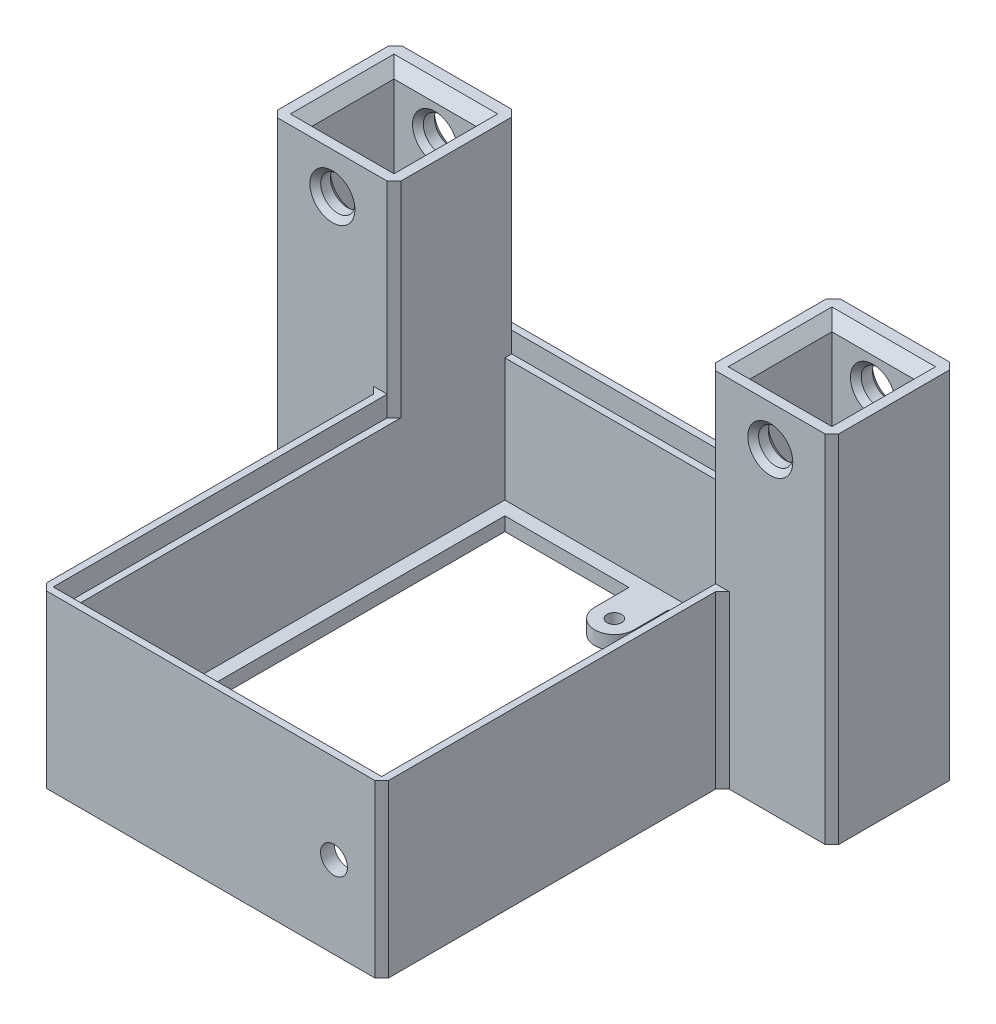
SolidWorks part; units mm, degrees
ref_plane "Front Plane" through (0, 0, 0) normal (0, 0, 1) x (1, 0, 0)
ref_plane "Top Plane" through (0, 0, 0) normal (0, 1, 0) x (1, 0, 0)
ref_plane "Right Plane" through (0, 0, 0) normal (1, 0, 0) x (0, 0, -1)
sketch "Sketch3" plane through (0, 0, 0) normal (0, 1, 0) x (-1, 0, 0)
  line L1 (0, 0) -> (63.5, 0)
  line L2 (0, 0) -> (0, 86.36)
  line L3 (0, 86.36) -> (63.5, 86.36)
  line L4 (63.5, 0) -> (63.5, 86.36)
  dimension "D1" = 86.36
  dimension "D2" = 63.5
extrude "Boss-Extrude2" add sketch "Sketch3" against normal blind 31.75
sketch "Sketch4" plane through (0, -31.75, 0) normal (0, -1, 0) x (1, 0, 0)
  line L1 (-2.54, 83.82) -> (-60.96, 83.82)
  line L2 (-2.54, 83.82) -> (-2.54, 2.54)
  line L3 (-2.54, 2.54) -> (-60.96, 2.54)
  line L4 (-60.96, 83.82) -> (-60.96, 2.54)
  line L8 (-63.5, 86.36) -> (0, 86.36) construction
  line L9 (0, 0) -> (-63.5, 0) construction
  line L10 (0, 86.36) -> (0, 0) construction
  line L11 (-63.5, 0) -> (-63.5, 86.36) construction
  dimension "D1" = 2.54
  dimension "D2" = 2.54
  dimension "D3" = 2.54
  dimension "D4" = 2.54
extrude "Cut-Extrude2" cut sketch "Sketch4" against normal offset from surface (27.94 mm away) 3.81 up to face at (-31.75, 0, 43.18)
sketch "Sketch5" plane through (-63.5, 0, 0) normal (1, 0, 0) x (0, 0, -1)
  line L0 (-86.36, -31.75) -> (-86.36, 0) construction
  line L5 (0, -31.75) -> (-86.36, -31.75) construction
  circle A0 centre (-76.327, -19.177) radius 5.715
  dimension "D1" = 11.43
  dimension "D2" = 6.858
  dimension "D3" = 4.318
extrude "Power Jack Hole" cut sketch "Sketch5" along normal up to next
sketch "Sketch6" plane through (-63.5, 0, 0) normal (-1, 0, 0) x (0, 0, 1)
  line L0 (46.54, 0) -> (46.54, 36.83)
  line L1 (46.54, 36.83) -> (0, 36.83)
  line L2 (0, 36.83) -> (0, 34.29)
  line L3 (0, 34.29) -> (44, 34.29)
  line L4 (44, 34.29) -> (44, 0)
  line L5 (0, 0) -> (86.36, 0) construction
  line L6 (44, 0) -> (46.54, 0)
  line L7 (0, -31.75) -> (0, 0) construction
  dimension "D1" = 44
  dimension "D2" = 34.29
  dimension "D3" = 2.54
  dimension "D4" = 2.54
extrude "Motor Mounting Shape" add sketch "Sketch6" against normal up to surface (63.5 mm away) up to face at (0, -15.875, 43.18)
sketch "Sketch8" plane through (0, 36.83, 0) normal (0, 1, 0) x (1, 0, 0)
  line L0 (-47.25, -38.77) -> (-16.25, -7.77) construction
  line L1 (-16.25, -38.77) -> (-47.25, -7.77) construction
  line L2 (-47.25, -38.77) -> (-47.25, -7.77) construction
  line L3 (-47.25, -7.77) -> (-16.25, -7.77) construction
  line L4 (-31.75, -46.54) -> (-31.75, 0) construction
  line L5 (0, -46.54) -> (-63.5, -46.54) construction
  line L6 (0, 0) -> (-63.5, 0) construction
  line L7 (-40.64, 0) -> (-22.86, 0)
  line L8 (-22.86, 0) -> (-22.86, -23.27)
  line L9 (-40.64, -23.27) -> (-40.64, 0)
  circle A1 centre (-47.25, -7.77) radius 1.6
  circle A2 centre (-16.25, -7.77) radius 1.6
  circle A3 centre (-16.25, -38.77) radius 1.6
  circle A4 centre (-47.25, -38.77) radius 1.6
  arc A6 (-40.64, -23.27) -> (-22.86, -23.27) centre (-31.75, -23.27) ccw
  point P10 (-31.75, -23.27)
  dimension "D2" = 3.2
  dimension "D3" = 8.89
  dimension "D1" = 31
extrude "Motor-Mounting-Holes" cut sketch "Sketch8" against normal up to next
sketch "Sketch13" plane through (0, 0, 0) normal (0, 1, 0) x (1, 0, 0)
  line L0 (-31.75, -85.09) -> (-31.75, -86.36) construction
  line L1 (-62.23, -1.27) -> (-1.27, -1.27)
  line L2 (-62.23, -1.27) -> (-62.23, -85.09)
  line L3 (-62.23, -85.09) -> (-1.27, -85.09)
  line L4 (-1.27, -1.27) -> (-1.27, -85.09)
  line L5 (-63.5, -86.36) -> (0, -86.36) construction
  line L6 (-63.5, -46.54) -> (-63.5, -86.36) construction
  line L7 (0, 0) -> (-63.5, 0) construction
  dimension "D1" = 1.27
  dimension "D2" = 1.27
  dimension "D3" = 1.27
extrude "Cut-Extrude7" cut sketch "Sketch13" against normal up to surface (3.81 mm away) up to face at (-31.75, -3.81, 43.18)
sketch "Sketch9" plane through (0, -31.75, 0) normal (0, -1, 0) x (1, 0, 0)
  line L0 (1.27, 23.114) -> (-2.54, 23.114)
  line L1 (1.27, 0) -> (20.32, 0)
  line L2 (1.27, 4.064) -> (1.27, 19.304)
  line L3 (1.27, 23.114) -> (20.32, 23.114)
  line L5 (20.32, 23.114) -> (20.32, 0)
  line L6 (1.27, 19.304) -> (16.51, 19.304)
  line L7 (16.51, 19.304) -> (16.51, 4.064)
  line L8 (16.51, 4.064) -> (1.27, 4.064)
  line L10 (-2.54, 23.114) -> (-2.54, 0)
  line L11 (-31.75, 86.36) -> (-31.75, 0) construction
  line L12 (-2.54, 0) -> (1.27, 0)
  line L13 (1.27, 19.304) -> (1.27, 4.064)
  line L14 (0, 0) -> (-63.5, 0) construction
  line L15 (-63.5, 86.36) -> (0, 86.36) construction
  line L16 (-80.01, 19.304) -> (-80.01, 4.064)
  line L17 (-80.01, 4.064) -> (-64.77, 4.064)
  line L18 (-64.77, 4.064) -> (-64.77, 19.304)
  line L19 (-64.77, 19.304) -> (-80.01, 19.304)
  line L20 (-60.96, 0) -> (-64.77, 0)
  line L21 (-60.96, 23.114) -> (-60.96, 0)
  line L22 (-64.77, 23.114) -> (-60.96, 23.114)
  line L23 (-64.77, 23.114) -> (-83.82, 23.114)
  line L24 (-83.82, 23.114) -> (-83.82, 0)
  line L25 (-64.77, 0) -> (-83.82, 0)
  line L26 (-2.54, 2.54) -> (-2.54, 83.82) construction
  dimension "D1" = 3.81
  dimension "D2" = 4.064
  dimension "D3" = 3.81
  dimension "D4" = 15.24
  dimension "D5" = 3.81
  dimension "D6" = 3.81
  dimension "D8" = 33.02
extrude "Boss-Extrude3" add sketch "Sketch9" against normal blind 66 contours L1 L5 L3 L0 L10 L12 | L13 L8 L7 L6 | L20 L25 L24 L23 L22 L21 | L16 L17 L18 L19
chamfer "Chamfer1" distance 2 angle 45 8 edges at (-64.77, 34.25, 11.684) (-72.39, 34.25, 4.064) (-80.01, 34.25, 11.684) (-72.39, 34.25, 19.304) (8.89, 34.25, 4.064) (1.27, 34.25, 11.684) (16.51, 34.25, 11.684) (8.89, 34.25, 19.304)
sketch "Sketch11" plane through (0, 0, 0) normal (1, 0, 0) x (0, 0, -1)
  line L0 (-44, 0) -> (-44, 34.29)
  line L1 (-44, 34.29) -> (0, 34.29)
  line L2 (0, 34.29) -> (0, 36.83)
  line L3 (0, 36.83) -> (-86.36, 36.83)
  line L4 (-86.36, 36.83) -> (-86.36, 0)
  line L5 (-86.36, 0) -> (-44, 0)
  line L6 (-46.54, 36.83) -> (0, 36.83) construction
extrude "Cut-Extrude5" cut sketch "Sketch11" against normal through all
sketch "Sketch12" plane through (0, 0, 23.114) normal (0, 0, 1) x (1, 0, 0)
  line L0 (20.32, -31.75) -> (0, -31.75) construction
  line L1 (-60.96, 34.25) -> (-60.96, -3.81) construction
  line L2 (-2.54, 34.25) -> (-2.54, -3.81) construction
  circle A0 centre (8.89, 26.67) radius 3.175
  circle A1 centre (-72.39, 26.67) radius 3.175
  dimension "D1" = 6.35
  dimension "D3" = 6.35
  dimension "D2" = 58.42
  dimension "D4" = 11.43
  dimension "D5" = 11.43
extrude "Leg Holes" cut sketch "Sketch12" against normal through all
chamfer "Chamfer2" distance 1 angle 45 8 edges at (12.065, 26.67, 23.114) (5.715, 26.67, 19.304) (12.065, 26.67, 4.064) (12.065, 26.67, 0) (-69.215, 26.67, 0) (-75.565, 26.67, 4.064) (-69.215, 26.67, 19.304) (-69.215, 26.67, 23.114)
sketch "Sketch14" plane through (0, -31.75, 0) normal (0, -1, 0) x (1, 0, 0)
  line L1 (-58.42, 81.28) -> (-5.08, 81.28)
  line L2 (-58.42, 81.28) -> (-58.42, 5.08)
  line L3 (-58.42, 5.08) -> (-5.08, 5.08)
  line L4 (-5.08, 81.28) -> (-5.08, 5.08)
  line L5 (-2.54, 83.82) -> (-60.96, 83.82) construction
  line L7 (-2.54, 2.54) -> (-2.54, 83.82) construction
  line L10 (-60.96, 83.82) -> (-2.54, 83.82)
  line L11 (-60.96, 83.82) -> (-60.96, 2.54)
  line L12 (-60.96, 2.54) -> (-2.54, 2.54)
  line L13 (-2.54, 83.82) -> (-2.54, 2.54)
  dimension "D1" = 2.54
  dimension "D2" = 2.54
  dimension "D3" = 2.54
  dimension "D4" = 2.54
extrude "Boss-Extrude5" add sketch "Sketch14" along normal blind 2.54 from offset 5.08 offset against normal yes
sketch "Sketch15" plane through (0, 0, 86.36) normal (0, 0, 1) x (1, 0, 0)
  line L0 (-63.5, -31.75) -> (0, -31.75) construction
  line L1 (0, -31.75) -> (0, 0) construction
  circle A0 centre (-8.85, -16.55) radius 2.5
  dimension "D1" = 5
  dimension "D2" = 12.7
  dimension "D3" = 6.35
extrude "Cut-Extrude8" cut sketch "Sketch15" against normal up to next
chamfer "Chamfer3" distance 1.27 angle 45 12 edges at (-63.5, -15.875, 86.36) (0, -15.875, 86.36) (0, -15.875, 23.114) (20.32, 1.25, 23.114) (20.32, 1.25, 0) (-2.54, 15.22, 23.114) (-2.54, 17.125, 0) (-60.96, 15.22, 23.114) (-60.96, 17.125, 0) (-83.82, 1.25, 0) (-83.82, 1.25, 23.114) (-63.5, -15.875, 23.114)
sketch "Sketch16" plane through (0, -29.21, 0) normal (0, -1, 0) x (1, 0, 0)
  line L0 (-35.386, 2.54) -> (-28.114, 2.54)
  line L1 (-60.96, 2.54) -> (-2.54, 2.54) construction
  line L2 (-28.114, 2.54) -> (-28.114, 11.43)
  line L3 (-35.386, 11.43) -> (-35.386, 2.54)
  line L4 (-60.96, 43.18) -> (-5.08, 43.18) construction
  line L5 (-60.96, 83.82) -> (-60.96, 2.54) construction
  line L6 (-5.08, 5.08) -> (-5.08, 81.28) construction
  line L7 (-58.42, 5.08) -> (-5.08, 5.08) construction
  line L8 (-35.386, 74.93) -> (-35.386, 83.82)
  line L9 (-35.386, 83.82) -> (-28.114, 83.82)
  line L10 (-28.114, 83.82) -> (-28.114, 74.93)
  arc A0 (-28.114, 11.43) -> (-35.386, 11.43) centre (-31.75, 11.43) ccw
  circle A1 centre (-31.75, 11.43) radius 1.35
  circle A2 centre (-31.75, 74.93) radius 1.35
  arc A3 (-28.114, 74.93) -> (-35.386, 74.93) centre (-31.75, 74.93) cw
  point P16 (-31.75, 2.54)
  point P23 (-31.75, 83.82)
  dimension "D1" = 2.7
  dimension "D2" = 2.286
  dimension "D3" = 6.35
extrude "Boss-Extrude6" add sketch "Sketch16" against normal up to surface (2.54 mm away) up to face at (-31.75, -26.67, 43.18)
